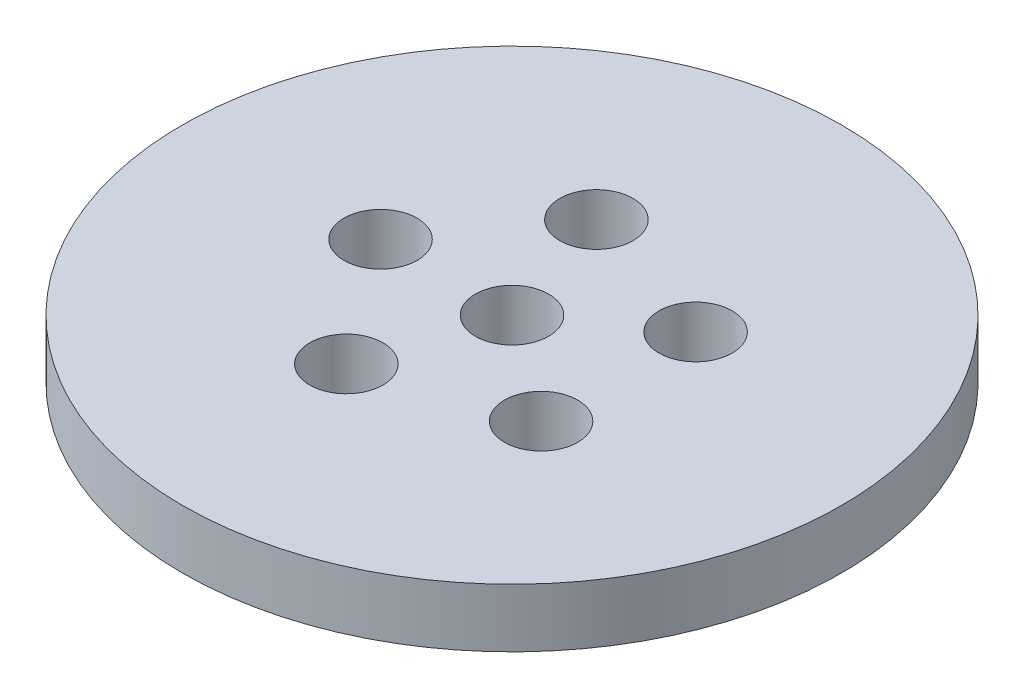
SolidWorks part; units mm, degrees
ref_plane "Front Plane" through (0, 0, 0) normal (0, 0, 1) x (1, 0, 0)
ref_plane "Top Plane" through (0, 0, 0) normal (0, 1, 0) x (1, 0, 0)
ref_plane "Right Plane" through (0, 0, 0) normal (1, 0, 0) x (0, 0, -1)
sketch "Sketch1" plane through (0, 0, 0) normal (0, 1, 0) x (1, 0, 0)
  circle A0 centre (0, 0) radius 90
  dimension "FLANGE_OD" = 180
extrude "Boss-Extrude1" add sketch "Sketch1" along normal blind 16
sketch "Sketch2" plane through (0, 0, 0) normal (0, 1, 0) x (1, 0, 0)
  circle A0 centre (0, 0) radius 10
  dimension "BORE_D" = 20
extrude "Cut-Extrude1" cut sketch "Sketch2" along normal through all
sketch "Sketch3" plane through (0, 16, 0) normal (0, 1, 0) x (1, 0, 0)
  circle A0 centre (0, 0) radius 35.9028 construction
  circle A1 centre (-35.9028, 0) radius 10
  dimension "BOLT_D" = 20
  dimension "BOLT_PCD" = 71.8056
extrude "Cut-Extrude2" cut sketch "Sketch3" against normal blind 14.8533
pattern_circular "CirPattern1" count 5 over 360 about axis through (0, 0, 0) along (0, 1, 0) of "Cut-Extrude2"
